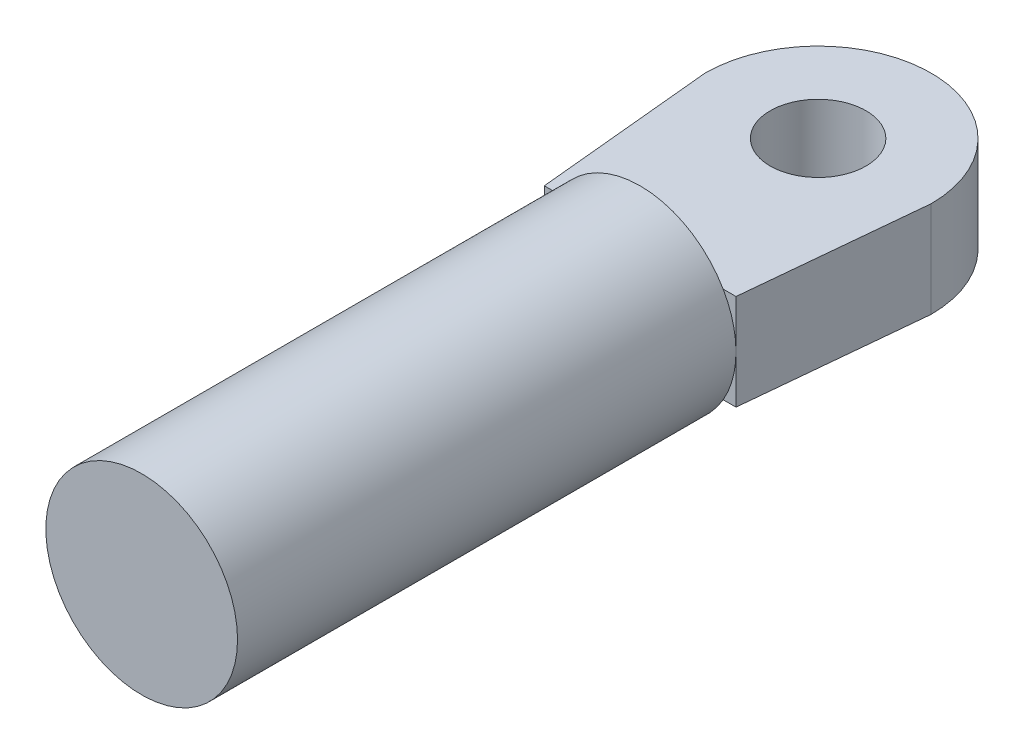
SolidWorks part; units mm, degrees
ref_plane "Спереди" through (0, 0, 0) normal (0, 0, 1) x (1, 0, 0)
ref_plane "Сверху" through (0, 0, 0) normal (0, 1, 0) x (1, 0, 0)
ref_plane "Справа" through (0, 0, 0) normal (1, 0, 0) x (0, 0, -1)
sketch "Эскиз1" plane through (0, 0, 0) normal (0, 0, 1) x (1, 0, 0)
  circle A0 centre (0, 0) radius 10
  dimension "D1" = 20
extrude "Бобышка-Вытянуть1" add sketch "Эскиз1" along normal blind 52
sketch "Эскиз2" plane through (0, 0, 0) normal (0, 1, 0) x (1, 0, 0)
  line L0 (-11.7983, 18.5665) -> (-10, 0)
  line L1 (10, 0) -> (-10, 0) construction
  line L2 (-10, 0) -> (10, 0)
  line L3 (10, 0) -> (11.7983, 18.5665)
  circle A0 centre (0, 18.5665) radius 5
  arc A1 (11.579, 16.3023) -> (-11.579, 16.3023) centre (0, 18.5665) ccw
  dimension "D1" = 10
extrude "Бобышка-Вытянуть2" add sketch "Эскиз2" along normal blind 5 and the other way blind 5 contours L3 A1 L0 L2 A0 region at (0, 0, -29.9803)
